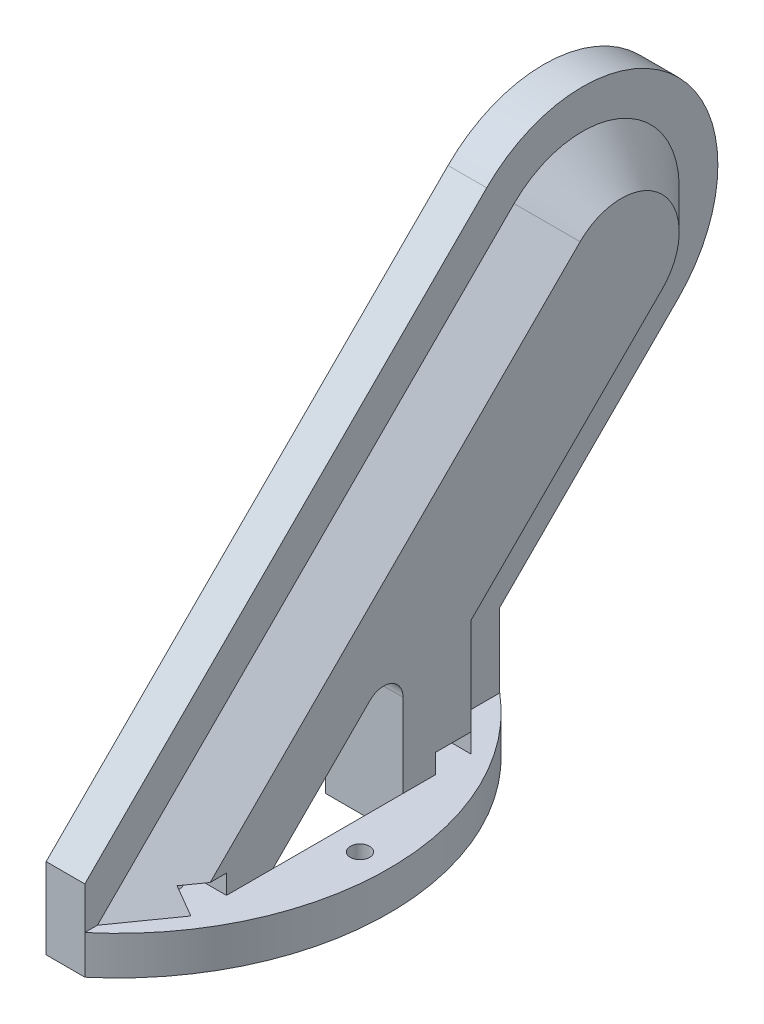
SolidWorks part; units mm, degrees
ref_plane "Front Plane" through (0, 0, 0) normal (0, 0, 1) x (1, 0, 0)
ref_plane "Top Plane" through (0, 0, 0) normal (0, 1, 0) x (1, 0, 0)
ref_plane "Right Plane" through (0, 0, 0) normal (1, 0, 0) x (0, 0, -1)
sketch "Sketch3" plane through (0, 0, 0) normal (0, 1, 0) x (1, 0, 0)
  line L0 (45, 53.619) -> (45, -53.619) construction
  line L1 (45, 53.619) -> (35, 53.619)
  line L2 (35, 53.619) -> (35, -53.619)
  line L3 (35, -53.619) -> (45, -53.619)
  circle A0 centre (0, 0) radius 70 construction
  circle A1 centre (0, 0) radius 30 construction
  arc A2 (45, 53.619) -> (45, -53.619) centre (0, 0) cw
  dimension "D1" = 140
  dimension "D2" = 60
  dimension "D3" = 45
  dimension "D4" = 10
extrude "Boss-Extrude3" add sketch "Sketch3" along normal blind 10
sketch "Sketch4" plane through (35, 0, 0) normal (-1, 0, 0) x (0, 0, 1)
  line L0 (0, 0) -> (-75, 0) construction
  line L1 (-75, 0) -> (-75, 100) construction
  line L2 (-53.619, 10) -> (-53.619, 29.1216)
  line L3 (-53.619, 29.1216) -> (-99.7487, 75.2513)
  line L4 (53.619, 10) -> (53.619, 20.8784)
  line L5 (53.619, 20.8784) -> (-50.2513, 124.7487)
  line L6 (-53.619, 10) -> (53.619, 10)
  circle A0 centre (-75, 100) radius 35
  circle A1 centre (-75, 100) radius 4
  line M8 (53.619, 10) -> (-53.619, 10)
  dimension "D3" = 70
  dimension "D6" = 8
  dimension "D1" = 75
  dimension "D2" = 100
  dimension "D4" = 45
  dimension "D5" = 45
extrude "Boss-Extrude4" add sketch "Sketch4" against normal blind 10 contours A0 L3 L2 L4 L5 M8 | A0 A1 region at (35, 46.4353, -17.5677) region at (35, 124.0487, -99.0487)
sketch "Sketch6" plane through (45, 0, 0) normal (1, 0, 0) x (0, 0, -1)
  line L1 (64.3934, 110.6066) -> (-36.2132, 10)
  line L2 (53.619, 10) -> (-53.619, 10) construction
  line L4 (85.6066, 89.3934) -> (6.2132, 10)
  line L5 (6.2132, 10) -> (-36.2132, 10)
  arc A0 (85.6066, 89.3934) -> (64.3934, 110.6066) centre (75, 100) ccw
  dimension "D1" = 30
extrude "Boss-Extrude6" add sketch "Sketch6" along normal blind 10
chamfer "Chamfer2" distance 30 angle 90 1 edges at (50, 10, -6.2132) first distance on face at (52.5, 10, 10)
chamfer "Chamfer3" distance 10 angle 45 4 edges at (45, 25, -36.2132) (45, 64.6967, -60.9099) (45, 110.6066, -85.6066) (45, 60.3033, -14.0901)
sketch "Sketch7" plane through (35, 0, 0) normal (-1, 0, 0) x (0, 0, 1)
  line L0 (53.619, 20.8784) -> (53.619, 0) construction
  line L1 (-53.619, 29.1216) -> (-53.619, 0) construction
  line L2 (53.619, 20.8784) -> (-50.2513, 124.7487) construction
  line L3 (-53.619, 29.1216) -> (-99.7487, 75.2513) construction
  line L4 (53.619, 20.8784) -> (53.619, 0) construction
  line L5 (-53.619, 29.1216) -> (-53.619, 0) construction
  line L6 (53.619, 20.8784) -> (-50.2513, 124.7487) construction
  line L7 (-53.619, 29.1216) -> (-99.7487, 75.2513) construction
  line L8 (18.619, 6.381) -> (18.619, 0)
  line L9 (18.619, 6.381) -> (-10.0835, 35.0835)
  line L10 (-18.619, 31.548) -> (-18.619, 0)
  line L11 (-18.619, 29.1216) -> (-18.619, 0) construction
  line L12 (18.619, 6.381) -> (-75, 100) construction
  line L13 (-18.619, 0) -> (18.619, 0)
  arc A0 (-50.2513, 124.7487) -> (-99.7487, 75.2513) centre (-75, 100) ccw construction
  arc A1 (-50.2513, 124.7487) -> (-99.7487, 75.2513) centre (-75, 100) ccw construction
  arc A2 (-18.619, 31.548) -> (-10.0835, 35.0835) centre (-13.619, 31.548) cw
  dimension "D3" = 5
  dimension "D2" = 35
  dimension "D1" = 35
extrude "Cut-Extrude1" cut sketch "Sketch7" against normal blind 20
sketch "Sketch8" plane through (0, 0, 0) normal (0, -1, 0) x (1, 0, 0)
  line L0 (45, 31.6228) -> (45, -31.6228) construction
  line L1 (45, 50.3553) -> (45, -57.3223) construction
  circle A0 centre (0, 0) radius 55 construction
  circle A1 centre (45, 31.6228) radius 2.5
  circle A2 centre (45, -31.6228) radius 2.5
  circle A3 centre (62.5, 0) radius 2.5
  dimension "D1" = 110
  dimension "D2" = 5
  dimension "D3" = 5
  dimension "D4" = 5
  dimension "D5" = 62.5
extrude "Cut-Extrude2" cut sketch "Sketch8" against normal blind 20
sketch "Sketch9" plane through (0, 0, 0) normal (0, -1, 0) x (1, 0, 0)
  line L1 (50.3405, 31.6228) -> (47.6702, 36.2478)
  line L2 (47.6702, 36.2478) -> (42.3298, 36.2478)
  line L3 (42.3298, 36.2478) -> (39.6595, 31.6228)
  line L4 (39.6595, 31.6228) -> (42.3298, 26.9978)
  line L5 (42.3298, 26.9978) -> (47.6702, 26.9978)
  line L6 (47.6702, 26.9978) -> (50.3405, 31.6228)
  line L7 (50.3405, -31.6228) -> (47.6702, -26.9978)
  line L8 (47.6702, -26.9978) -> (42.3298, -26.9978)
  line L9 (42.3298, -26.9978) -> (39.6595, -31.6228)
  line L10 (39.6595, -31.6228) -> (42.3298, -36.2478)
  line L11 (42.3298, -36.2478) -> (47.6702, -36.2478)
  line L12 (47.6702, -36.2478) -> (50.3405, -31.6228)
  line L16 (47.6702, 36.2478) -> (55, 36.2132)
  line L17 (55, 36.2132) -> (55, 26.9978)
  line L18 (55, 36.2132) -> (55, 15) construction
  line L19 (55, 26.9978) -> (47.6702, 26.9978)
  line L20 (47.6702, -26.9978) -> (55, -26.9978)
  line L21 (55, -18.619) -> (55, -36.2132) construction
  line L22 (55, -26.9978) -> (55, -36.2132)
  line L23 (55, -36.2132) -> (47.6702, -36.2478)
  circle A0 centre (45, 31.6228) radius 4.625 construction
  circle A1 centre (45, -31.6228) radius 4.625 construction
  circle M7 centre (45, 31.6228) radius 2.5
  circle M8 centre (45, -31.6228) radius 2.5
  dimension "D1" = 9.25
  dimension "D2" = 9.25
extrude "Cut-Extrude4" cut sketch "Sketch9" against normal blind 5 from offset 10 contours L19 L17 L16 L1 L6 | L5 L6 L1 L2 L3 L4 M7 | L23 L22 L20 L7 L12 | L11 L12 L7 L8 L9 L10 M8 region at (48.883, 0, 29.3809) region at (51.9517, 0, 31.6122) region at (48.883, 0, -33.8646) region at (51.9517, 0, -31.6122) offset against normal yes
sketch "Sketch10" plane through (35, 0, 0) normal (-1, 0, 0) x (0, 0, 1)
  circle A0 centre (-75, 100) radius 11
  dimension "D1" = 22
extrude "Cut-Extrude5" cut sketch "Sketch10" against normal blind 5
